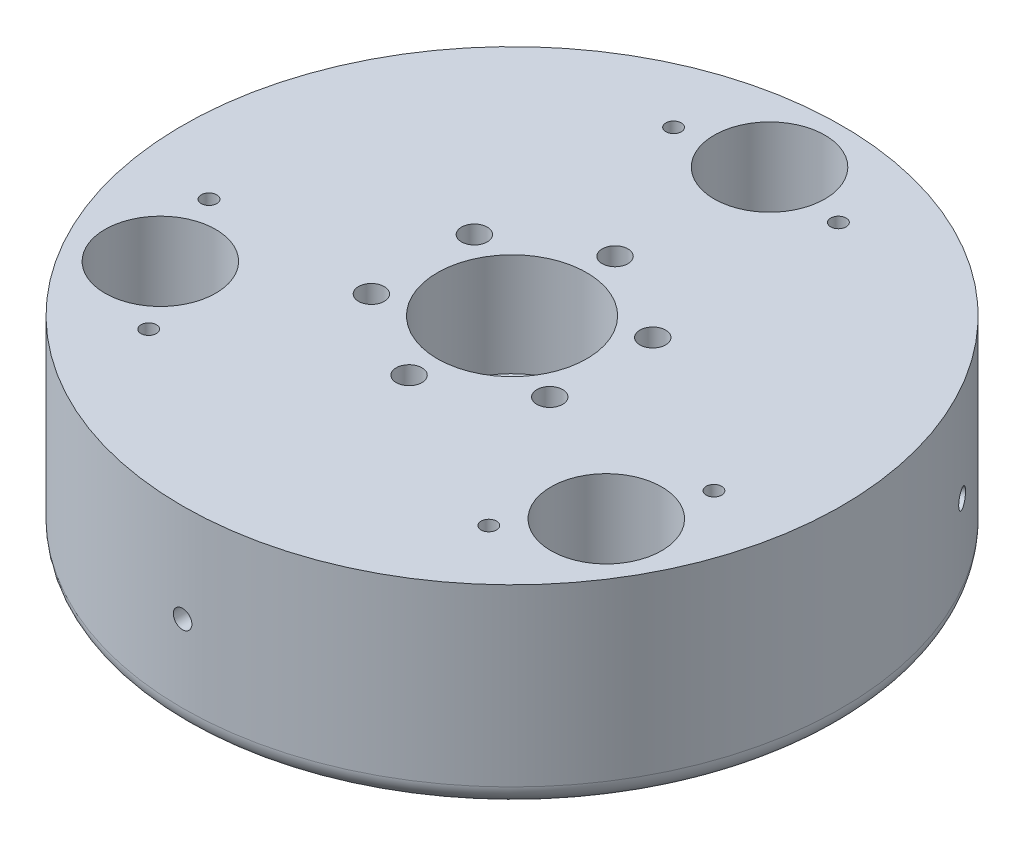
SolidWorks part; units mm, degrees
ref_plane "Спереди" through (0, 0, 0) normal (0, 0, 1) x (1, 0, 0)
ref_plane "Сверху" through (0, 0, 0) normal (0, 1, 0) x (1, 0, 0)
ref_plane "Справа" through (0, 0, 0) normal (1, 0, 0) x (0, 0, -1)
sketch "Эскиз1" plane through (0, 0, 0) normal (0, 1, 0) x (1, 0, 0)
  circle A3 centre (0, 0) radius 32
  circle A4 centre (0, 0) radius 4
  circle A6 centre (0, 0) radius 25 construction
  circle A7 centre (0, 25) radius 3
  circle A8 centre (21.6506, -12.5) radius 3
  circle A9 centre (-21.6506, -12.5) radius 3
  dimension "D4" = 64
  dimension "D1" = 8
  dimension "D2" = 50
  dimension "D3" = 6
  dimension "D5" = 3
extrude "Бобышка-Вытянуть1" add sketch "Эскиз1" along normal blind 19
fillet "Скругление1" radius 2 1 edges at (0, 0, 32)
sketch "Эскиз2" plane through (0, 19, 0) normal (0, 1, 0) x (1, 0, 0)
  circle A0 centre (0, 25) radius 5.375
  circle A2 centre (21.6506, -12.5) radius 5.375
  circle A3 centre (-21.6506, -12.5) radius 5.375
  circle A4 centre (-21.6506, -12.5) radius 3 construction
  dimension "D1" = 10.75
extrude "Вырез-Вытянуть1" cut sketch "Эскиз2" against normal blind 15.5
sketch "Эскиз3" plane through (0, 0, 0) normal (0, -1, 0) x (1, 0, 0)
  circle A0 centre (0, 0) radius 25 construction
  circle A1 centre (0, 25) radius 2.625
  circle A2 centre (21.6506, -12.5) radius 2.625
  circle A3 centre (-21.6506, -12.5) radius 2.625
  dimension "D1" = 5.25
extrude "Вырез-Вытянуть2" cut sketch "Эскиз3" against normal blind 15
sketch "Эскиз4" plane through (0, 19, 0) normal (0, 1, 0) x (1, 0, 0)
  circle A0 centre (0, 0) radius 10 construction
  circle A1 centre (0, 10) radius 1.25
  circle A2 centre (8.6603, 5) radius 1.25
  circle A3 centre (8.6603, -5) radius 1.25
  circle A4 centre (0, -10) radius 1.25
  circle A5 centre (-8.6603, -5) radius 1.25
  circle A6 centre (-8.6603, 5) radius 1.25
  dimension "D3" = 6
  dimension "D1" = 20
  dimension "D2" = 2.5
extrude "Вырез-Вытянуть3" cut sketch "Эскиз4" against normal through all
sketch "Эскиз7" plane through (0, 0, 0) normal (0, -1, 0) x (1, 0, 0)
  circle A0 centre (0, 10) radius 1.95 construction
  circle A7 centre (8.6603, 5) radius 1.95
  circle A8 centre (8.6603, -5) radius 1.95 construction
  circle A9 centre (0, -10) radius 1.95
  circle A10 centre (-8.6603, -5) radius 1.95 construction
  circle A11 centre (-8.6603, 5) radius 1.95
  circle A12 centre (8.6603, 5) radius 1.25 construction
  dimension "D1" = 3.9
  dimension "D2" = 6
extrude "Вырез-Вытянуть5" cut sketch "Эскиз7" against normal offset from surface (3 mm away) 16 up to face at (0, 19, -8.75)
chamfer "Фаска1" distance 1 angle 45 7 edges at (21.6506, 0, -15.125) (0, 0, -22) (-21.6506, 0, -15.125) (-21.6506, 0, 15.5) (0, 0, 22.375) (21.6506, 0, 15.5) (0, 0, 4)
sketch "Эскиз8" plane through (0, 19, 0) normal (0, 1, 0) x (1, 0, 0)
  circle A0 centre (0, 0) radius 7.25
  dimension "D1" = 14.5
extrude "Вырез-Вытянуть6" cut sketch "Эскиз8" against normal blind 10
sketch "Эскиз9" plane through (0, 19, 0) normal (0, 1, 0) x (1, 0, 0)
  line L0 (0, 0) -> (0, 25) construction
  line L1 (-8, 23.6854) -> (8, 23.6854) construction
  circle A0 centre (0, 0) radius 25 construction
  circle A1 centre (-8, 23.6854) radius 0.75
  circle A2 centre (8, 23.6854) radius 0.75
  circle A3 centre (16.5122, -18.7709) radius 0.75
  circle A4 centre (24.5122, -4.9145) radius 0.75
  circle A5 centre (-24.5122, -4.9145) radius 0.75
  circle A6 centre (-16.5122, -18.7709) radius 0.75
  dimension "D1" = 16
  dimension "D2" = 1.5
  dimension "D3" = 1.5
extrude "Вырез-Вытянуть7" cut sketch "Эскиз9" against normal through all
ref_plane "Плоскость1" through (0, 0, 32) normal (0, 0, 1) x (1, 0, 0)
sketch "Эскиз11" plane through (0, 0, 32) normal (0, 0, 1) x (1, 0, 0)
  line L0 (0, 0) -> (0, 19) construction
  line L1 (-30, 0) -> (30, 0) construction
  line L2 (1.25, 19) -> (-1.25, 19) construction
  circle A0 centre (0, 9.5) radius 0.9
  dimension "D1" = 1.8
extrude "Вырез-Вытянуть9" cut sketch "Эскиз11" against normal up to next
pattern_circular "Круговой массив7" count 3 over 360 about axis through (0, 19, 0) along (0, -1, 0) of "Вырез-Вытянуть9" reverse direction yes
equation "\"motor_diameter\"= 30"
equation "\"mm_diameter\"= IIF ( \"motor_diameter\" < 34 , 41 , \"motor_diameter\" + 8 )"
equation "\"upper_shafts_diameter\"= 5"
equation "\"upper_shats_length\"= 180"
equation "\"upper_bearing_d1\"= 10"
equation "\"upper_bearing_d2\"= 5"
equation "\"upper_bearing_h\"= 15"
equation "\"lower_shafts_diameter\"= 5"
equation "\"lower_shafts_length\"= 180"
equation "\"lower_bearing_d1\"= 10"
equation "\"lower_bearing_d2\"= 5"
equation "\"lower_bearing_h\"= 15"
equation "\"print_offset\"= 0.5"
equation "\"bh_screws_d\"= 2"
equation "\"bh_screws_h\"= 20"
equation "\"bh_screws_hh_d\"= 3.4"
equation "\"bh_screws_hh_h\"= 2"
equation "\"bh_nut_d\"= 3.8"
equation "\"bh_nut_h\"= 2"
equation "\"motor_screws_d\"= 3"
equation "\"motor_screws_h\"= 16"
equation "\"motor_screws_hh_d\"= 5.5"
equation "\"motor_screws_hh_h\"= 3"
equation "\"plate_hole_distance\"= 25.4"
equation "\"plate_screws_d\"= 6.5"
equation "\"shafts_diameter\"= IIF ( \"mm_diameter\" < 42 , 42 + 8 , \"mm_diameter\" + 8 )"
equation "\"D4@Эскиз1\"= \"system_radius\" * 2"
equation "\"central_hole_diameter\"= 8"
equation "\"bh_thikness\"= 4"
equation "\"D1@Эскиз1\"=\"central_hole_diameter\""
equation "\"D2@Эскиз1\"=\"shafts_diameter\""
equation "\"D3@Эскиз1\" = \"lower_shafts_diameter\" + 1"
equation "\"D1@Бобышка-Вытянуть1\" = \"bh_thikness\" + \"lower_bearing_h\""
equation "\"D1@Эскиз2\" = \"lower_bearing_d1\" + \"print_offset\" * 1.5"
equation "\"D1@Вырез-Вытянуть1\" = \"lower_bearing_h\" + \"print_offset\""
equation "\"D1@Эскиз3\" = \"upper_shafts_diameter\" + \"print_offset\" / 2"
equation "\"D1@Вырез-Вытянуть2\"= \"upper_bearing_h\""
equation "\"D2@Эскиз4\"=\"bh_screws_d\"+\"print_offset\""
equation "\"D1@Вырез-Вытянуть5\"=\"bh_screws_h\"-\"bh_thikness\""
equation "\"D1@Эскиз7\"=\"bh_screws_hh_d\"+\"print_offset\""
equation "\"D1@Вырез-Вытянуть6\"=14-\"bh_thikness\""
equation "\"D2@Эскиз9\"=\"bh_screws_d\"-\"print_offset\""
equation "\"D3@Эскиз9\"=\"D2@Эскиз9\""
equation "\"ends_screws_d\"= 4"
equation "\"ends_screws_h\"= 16"
equation "\"ends_screws_hh_d\"= 6.7"
equation "\"ends_screws_hh_h\"= 4.1"
equation "\"ends_nut_d\"= 6.8"
equation "\"ends_nut_h\"= 3"
equation "\"system_radius\" = ( \"shafts_diameter\" + 12 + \"bh_thikness\" / 2 ) / 2"
equation "\"encoder_distance\"= \"system_radius\" + 4"
equation "\"tape_position\"= \"encoder_distance\" - 2 + 3.9 + 1.7 / 2"
equation "\"ft_sensor_d1\" = 9.8"
equation "\"ft_sensor_d2\"= 24.9"
equation "\"ft_sensor_h\"= 7"
equation "\"carbon_pipe_d\"= 14"
equation "\"D1@Эскиз8\"=\"print_offset\"+14.00мм"
equation "\"D1@Эскиз11\"=\"bh_screws_d\"-0.2"
